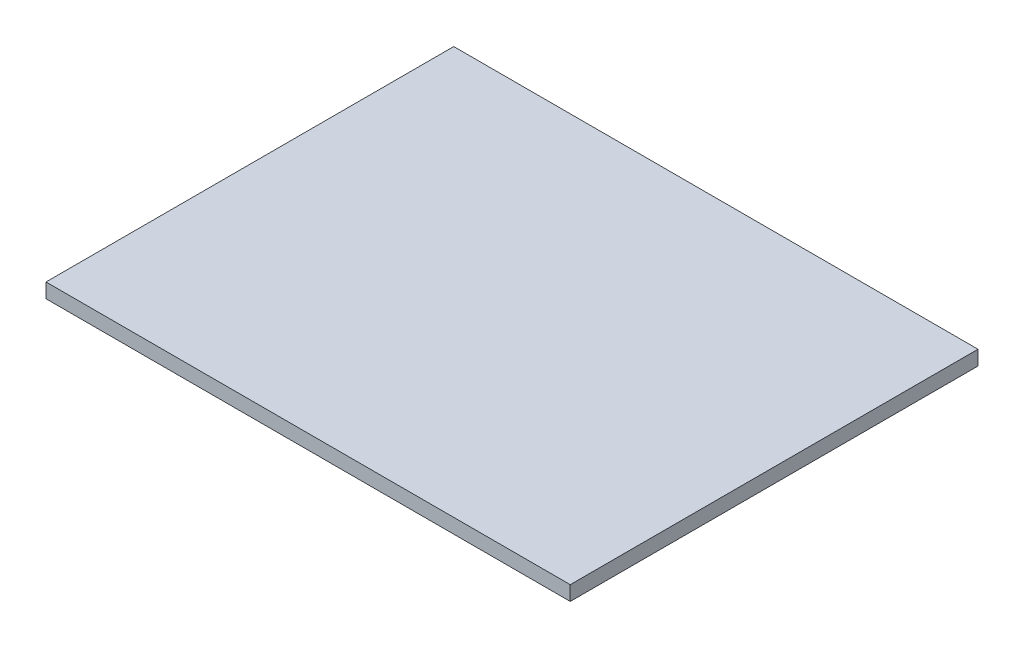
SolidWorks part; units mm, degrees
ref_plane "Front Plane" through (0, 0, 0) normal (0, 0, 1) x (1, 0, 0)
ref_plane "Top Plane" through (0, 0, 0) normal (0, 1, 0) x (1, 0, 0)
ref_plane "Right Plane" through (0, 0, 0) normal (1, 0, 0) x (0, 0, -1)
sketch "Sketch1" plane through (0, 0, 0) normal (0, 1, 0) x (1, 0, 0)
  line L1 (90, -70) -> (-90, -70)
  line L2 (90, -70) -> (90, 70)
  line L3 (90, 70) -> (-90, 70)
  line L4 (-90, -70) -> (-90, 70)
  line L5 (90, -70) -> (-90, 70) construction
  line L6 (90, 70) -> (-90, -70) construction
  point P0 (0, 0)
  dimension "D1" = 180
  dimension "D2" = 140
extrude "Body" add sketch "Sketch1" along normal blind 5
